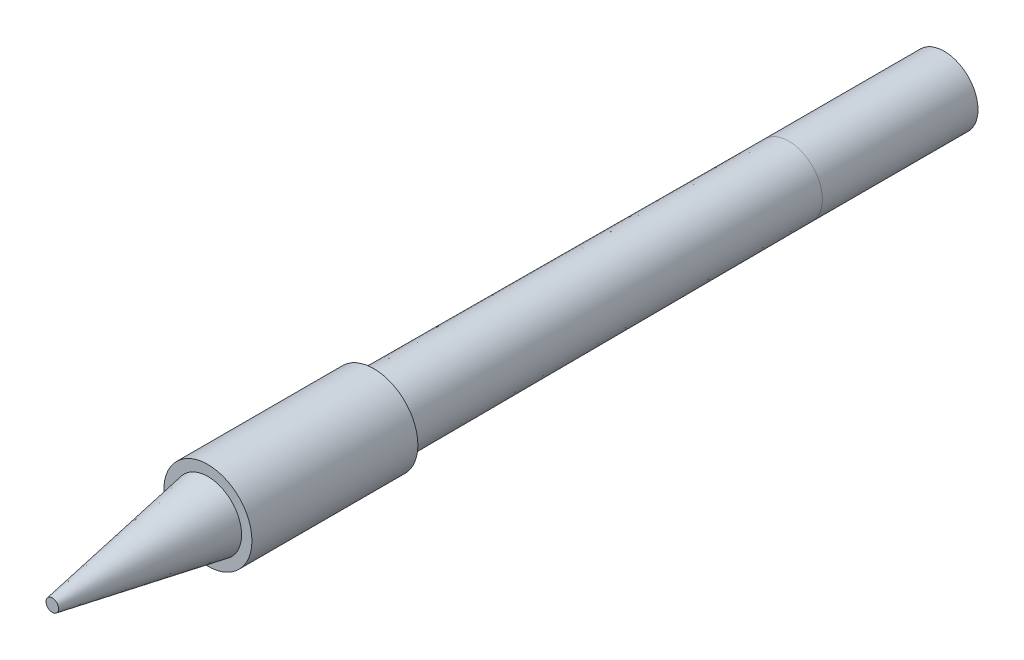
SolidWorks part; units mm, degrees
ref_plane "前视基准面" through (0, 0, 0) normal (0, 0, 1) x (1, 0, 0)
ref_plane "上视基准面" through (0, 0, 0) normal (0, 1, 0) x (1, 0, 0)
ref_plane "右视基准面" through (0, 0, 0) normal (1, 0, 0) x (0, 0, -1)
other "Configuration Table"
sketch "Sketch1" plane through (0, 0, 0) normal (0, 0, 1) x (1, 0, 0)
  circle A0 centre (0, 0) radius 6.5
extrude "Boss-Extrude1" add sketch "Sketch1" along normal blind 80 draft 0.2 draft outward yes
extrude "Boss-Extrude2" add sketch "Sketch1<2>" against normal blind 30
sketch "Sketch1<2>" plane through (0, 0, 0) normal (0, 0, 1) x (1, 0, 0) same geometry as "Sketch1"
sketch "Sketch2" plane through (0, 0, 80) normal (0, 0, 1) x (1, 0, 0)
  circle A0 centre (0, 0) radius 8.5
extrude "Boss-Extrude3" add sketch "Sketch2" along normal blind 32
sketch "Sketch3" plane through (0, 0, 112) normal (0, 0, 1) x (1, 0, 0)
  circle A0 centre (0, 0) radius 6.5
extrude "Boss-Extrude4" add sketch "Sketch3" along normal blind 30 draft 10
